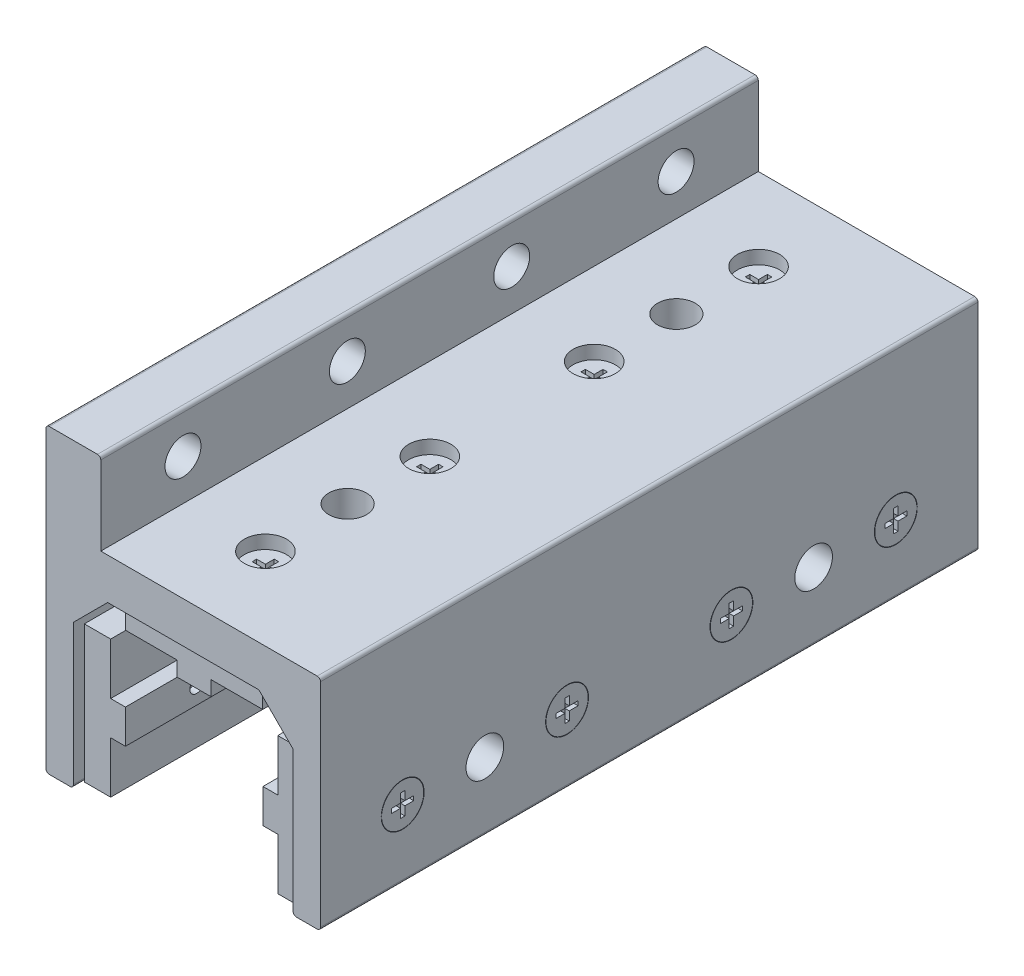
SolidWorks part; units mm, degrees
ref_plane "Front Plane" through (0, 0, 0) normal (0, 0, 1) x (1, 0, 0)
ref_plane "Top Plane" through (0, 0, 0) normal (0, 1, 0) x (1, 0, 0)
ref_plane "Right Plane" through (0, 0, 0) normal (1, 0, 0) x (0, 0, -1)
sketch "Sketch1" plane through (0, 0, 0) normal (0, 0, 1) x (1, 0, 0)
  line L0 (0, -34.925) -> (0, 34.925) construction
  line L1 (-31.8135, 0) -> (31.8135, 0) construction
  line L2 (-31.8135, 34.925) -> (-31.8135, -34.925) construction
  line L3 (-31.8135, -34.925) -> (-25.4635, -34.925) construction
  line L4 (-25.4635, -34.925) -> (-25.4635, -1.5875) construction
  line L5 (-25.4635, -1.5875) -> (-17.526, 6.35) construction
  line L6 (-17.526, 6.35) -> (17.526, 6.35) construction
  line L7 (17.526, 6.35) -> (25.4635, -1.5875) construction
  line L8 (25.4635, -1.5875) -> (25.4635, -34.925) construction
  line L9 (25.4635, -34.925) -> (31.8135, -34.925) construction
  line L10 (31.8135, -34.925) -> (31.8135, 15.875) construction
  line L11 (31.8135, 15.875) -> (-19.1135, 15.875) construction
  line L12 (-19.1135, 15.875) -> (-19.1135, 34.925) construction
  line L13 (-19.1135, 34.925) -> (-31.8135, 34.925) construction
  line L14 (-25.4635, -3.175) -> (-19.3675, -3.175) construction
  line L15 (-19.3675, -3.175) -> (-19.3675, -15.113) construction
  line L16 (-19.3675, -15.113) -> (-15.9385, -15.113) construction
  line L17 (-15.9385, -15.113) -> (-15.9385, -22.987) construction
  line L18 (-15.9385, -22.987) -> (-19.3675, -22.987) construction
  line L19 (-19.3675, -22.987) -> (-19.3675, -34.925) construction
  line L20 (-19.3675, -34.925) -> (-25.4635, -34.925) construction
  line L21 (-19.3675, -15.113) -> (-19.3675, -22.987) construction
  line L22 (-15.9385, -19.05) -> (-25.4635, -19.05) construction
  line L23 (-25.4635, -19.05) -> (25.4635, -19.05) construction
  point P4 (0, 0)
  point P7 (0, 0)
  point P30 (0, 6.35)
  point P31 (0, 12.7)
  dimension "Length (B)" = 69.85
  dimension "Length (A)" = 63.627
  dimension "Mounting Hole Depth" = 12.7
  dimension "D1" = 6.35
  dimension "Chamfer" = 7.9375
  dimension "D2" = 45
  dimension "Inner Height" = 41.275
  dimension "Pad Width" = 31.75
  dimension "Pad Height" = 9.525
  dimension "Pad Thickness" = 6.096
  dimension "Pad Rail" = 7.874
  dimension "Countersink Depth" = 3.175
  dimension "Length (C)" = 50.8
sketch "Sketch2" plane through (0, 0, 0) normal (1, 0, 0) x (0, 0, -1)
  line L0 (-76.2, 0) -> (76.2, 0) construction
  line L1 (-76.2, 15.875) -> (76.2, 15.875) construction
  line L2 (-76.2, 34.925) -> (76.2, 34.925) construction
  line L3 (-76.2, 34.925) -> (-76.2, -34.925) construction
  line L4 (-76.2, -34.925) -> (76.2, -34.925) construction
  line L5 (76.2, 34.925) -> (76.2, -34.925) construction
  line L6 (0, 34.925) -> (-76.2, 15.875) construction
  line L7 (0, 34.925) -> (0, 15.875) construction
  line L8 (-57.15, 25.4) -> (-19.05, 25.4) construction
  line L9 (-76.2, -19.05) -> (76.2, -19.05) construction
  line L10 (-57.6605, -21.6027) -> (-56.6395, -21.6027) construction
  line L11 (-57.6605, -21.6027) -> (-57.6605, -16.4973) construction
  line L12 (-57.6605, -16.4973) -> (-56.6395, -16.4973) construction
  line L13 (-56.6395, -21.6027) -> (-56.6395, -16.4973) construction
  line L14 (-57.15, -16.4973) -> (-57.15, -21.6027) construction
  line L15 (-57.6605, -19.05) -> (-56.6395, -19.05) construction
  line L16 (-59.7027, -18.5395) -> (-54.5973, -18.5395) construction
  line L17 (-59.7027, -18.5395) -> (-59.7027, -19.5605) construction
  line L18 (-59.7027, -19.5605) -> (-54.5973, -19.5605) construction
  line L19 (-54.5973, -18.5395) -> (-54.5973, -19.5605) construction
  line L20 (-57.15, -19.5605) -> (-57.15, -18.5395) construction
  line L21 (-59.7027, -19.05) -> (-54.5973, -19.05) construction
  line L22 (-38.1, 25.4) -> (-38.1, -19.05) construction
  circle A0 centre (-57.15, 25.4) radius 4.1656 construction
  circle A1 centre (-19.05, 25.4) radius 4.1656 construction
  circle A2 centre (-38.1, -19.05) radius 4.3688 construction
  circle A3 centre (-57.15, -19.05) radius 2.5527 construction
  circle A4 centre (-19.05, -19.05) radius 2.5527 construction
  circle A5 centre (-19.05, -19.05) radius 1.5875
  circle A6 centre (-57.15, -19.05) radius 1.5875
  point P12 (0, 15.875)
  point P39 (-38.1, 25.4)
  point P40 (0, -19.05)
  point P44 (-38.1, 25.4)
  dimension "Mounting Hole Diameter" = 8.3312
  dimension "Hole Diameter 2" = 8.7376
  dimension "D1" = 5.1054
  dimension "Pilot Hole" = 3.175
  dimension "Length" = 152.4
  dimension "Mounting Hole Spacing" = 38.1
  dimension "D2" = 1.0211
sketch "Sketch3" plane through (0, 0, 0) normal (0, 1, 0) x (1, 0, 0)
  line L0 (0, -76.2) -> (0, 76.2) construction
  line L5 (0, -76.2) -> (0, 76.2) construction
  circle A0 centre (0, -19.05) radius 2.5527 construction
  circle A1 centre (0, -57.15) radius 2.5527 construction
  circle A2 centre (0, -38.1) radius 4.3688 construction
  circle A3 centre (0, -19.05) radius 4.8895 construction
  circle A4 centre (0, -57.15) radius 4.8895 construction
  dimension "D1" = 8.7376
  dimension "D2" = 5.1054
  dimension "Countersink Diameter" = 9.779
ref_plane "Plane1" through (0, 0, 57.15) normal (0, 0, 1) x (1, 0, 0)
sketch "Sketch11" plane through (0, 0, 57.15) normal (0, 0, 1) x (1, 0, 0)
  line L0 (-25.4635, -19.05) -> (-31.8135, -19.05) construction
  line L1 (-31.8135, 34.925) -> (-31.8135, -34.925) construction
  line L2 (-31.8135, -14.1605) -> (-31.8135, -23.9395) construction
  line L3 (-31.8135, -14.1605) -> (-29.7355, -16.637) construction
  line L4 (-29.7355, -16.637) -> (-29.7355, -21.463) construction
  line L5 (-29.7355, -21.463) -> (-31.8135, -23.9395) construction
  line L6 (-29.7355, -16.637) -> (-17.653, -16.637) construction
  line L7 (-17.653, -16.637) -> (-17.653, -15.113) construction
  line L8 (-19.3675, -15.113) -> (-15.9385, -15.113) construction
  point P7 (-30.7745, -15.3987)
  dimension "D1" = 9.779
  dimension "D2" = 100
  dimension "D3" = 4.826
sketch "Sketch4" plane through (0, 0, 0) normal (0, 0, 1) x (1, 0, 0)
  line L0 (-31.8135, -34.925) -> (-25.4635, -34.925) construction
  line L1 (-31.8135, 34.925) -> (-31.8135, -34.925) construction
  line L2 (-19.1135, 34.925) -> (-31.8135, 34.925) construction
  line L3 (-19.1135, 15.875) -> (-19.1135, 34.925) construction
  line L4 (31.8135, 15.875) -> (-19.1135, 15.875) construction
  line L5 (31.8135, -34.925) -> (31.8135, 15.875) construction
  line L6 (25.4635, -34.925) -> (31.8135, -34.925) construction
  line L7 (25.4635, -1.5875) -> (25.4635, -34.925) construction
  line L8 (17.526, 6.35) -> (25.4635, -1.5875) construction
  line L9 (-17.526, 6.35) -> (17.526, 6.35) construction
  line L10 (-25.4635, -1.5875) -> (-17.526, 6.35) construction
  line L11 (-25.4635, -34.925) -> (-25.4635, -1.5875) construction
  line L12 (-31.8135, -34.925) -> (-25.4635, -34.925)
  line L13 (-31.8135, 34.925) -> (-31.8135, -34.925)
  line L14 (-19.1135, 34.925) -> (-31.8135, 34.925)
  line L15 (-19.1135, 15.875) -> (-19.1135, 34.925)
  line L16 (31.8135, 15.875) -> (-19.1135, 15.875)
  line L17 (31.8135, -34.925) -> (31.8135, 15.875)
  line L18 (25.4635, -34.925) -> (31.8135, -34.925)
  line L19 (25.4635, -1.5875) -> (25.4635, -34.925)
  line L20 (17.526, 6.35) -> (25.4635, -1.5875)
  line L21 (-17.526, 6.35) -> (17.526, 6.35)
  line L22 (-25.4635, -1.5875) -> (-17.526, 6.35)
  line L23 (-25.4635, -34.925) -> (-25.4635, -1.5875)
extrude "Boss-Extrude1" add sketch "Sketch4" along normal up to vertex (76.2 mm away) up to point (0, 34.925, 76.2)
sketch "Sketch5" plane through (0, 0, 0) normal (0, 0, 1) x (1, 0, 0)
  line L0 (-25.4635, -3.175) -> (-25.4635, -34.925)
  line L1 (-25.4635, -34.925) -> (-19.3675, -34.925)
  line L2 (-19.3675, -34.925) -> (-19.3675, -22.987)
  line L3 (-19.3675, -22.987) -> (-15.9385, -22.987)
  line L4 (-15.9385, -22.987) -> (-15.9385, -15.113)
  line L5 (-15.9385, -15.113) -> (-19.3675, -15.113)
  line L6 (-19.3675, -15.113) -> (-19.3675, -3.175)
  line L7 (-19.3675, -3.175) -> (-25.4635, -3.175)
extrude "Boss-Extrude2" add sketch "Sketch5" along normal offset from surface (71.12 mm away) 2.54 from offset 2.54 separate body up to face at (-3.1856, -2.3812, 76.2)
sketch "Sketch6" plane through (0, 0, 0) normal (1, 0, 0) x (0, 0, -1)
  circle A0 centre (-57.15, -19.05) radius 2.5527 construction
  circle A1 centre (-38.1, -19.05) radius 4.3688 construction
  circle A2 centre (-19.05, -19.05) radius 2.5527 construction
  circle A3 centre (-19.05, 25.4) radius 4.1656 construction
  circle A4 centre (-57.15, 25.4) radius 4.1656 construction
  circle A5 centre (-57.15, -19.05) radius 2.5527
  circle A6 centre (-38.1, -19.05) radius 4.3688
  circle A7 centre (-19.05, -19.05) radius 2.5527
  circle A8 centre (-19.05, 25.4) radius 4.1656
  circle A9 centre (-57.15, 25.4) radius 4.1656
extrude "Cut-Extrude1" cut sketch "Sketch6" against normal through all both and the other way through all
sketch "Sketch7" plane through (0, 0, 0) normal (1, 0, 0) x (0, 0, -1)
  line L1 (-42.4688, -23.4188) -> (-33.7312, -23.4188)
  line L2 (-42.4688, -23.4188) -> (-42.4688, -14.6812)
  line L3 (-42.4688, -14.6812) -> (-33.7312, -14.6812)
  line L4 (-33.7312, -23.4188) -> (-33.7312, -14.6812)
  line L5 (-38.1, -14.6812) -> (-38.1, -23.4188) construction
  line L6 (-42.4688, -19.05) -> (-33.7312, -19.05) construction
  circle A0 centre (-57.15, -19.05) radius 1.5875 construction
  circle A1 centre (-57.15, -19.05) radius 1.5875
  circle A2 centre (-19.05, -19.05) radius 1.5875 construction
  circle A3 centre (-19.05, -19.05) radius 1.5875
  circle A4 centre (-38.1, -19.05) radius 4.3688 construction
  point P6 (-38.1, -19.05)
extrude "Cut-Extrude2" cut sketch "Sketch7" against normal through all
sketch "Sketch8" plane through (0, 15.875, 0) normal (0, 1, 0) x (1, 0, 0)
  circle A0 centre (0, -19.05) radius 2.5527 construction
  circle A1 centre (0, -57.15) radius 2.5527 construction
  circle A2 centre (0, -19.05) radius 2.5527
  circle A3 centre (0, -57.15) radius 2.5527
extrude "Cut-Extrude3" cut sketch "Sketch8" against normal up to vertex (9.525 mm away) up to point (0, 6.35, 0)
sketch "Sketch9" plane through (0, 15.875, 0) normal (0, 1, 0) x (1, 0, 0)
  circle A0 centre (0, -19.05) radius 4.8895 construction
  circle A1 centre (0, -19.05) radius 4.8895
  circle A2 centre (0, -57.15) radius 4.8895 construction
  circle A3 centre (0, -57.15) radius 4.8895
extrude "Cut-Extrude4" cut sketch "Sketch9" against normal up to vertex (3.175 mm away) up to point (0, 12.7, 0)
chamfer "Chamfer1" distance 2.032 angle 50 6 edges at (-31.8135, -19.05, 16.4973) (-31.8135, -19.05, 54.5973) (31.8135, -19.05, 16.4973) (31.8135, -19.05, 54.5973) (-2.5527, 12.7, 57.15) (-2.5527, 12.7, 19.05)
sketch "Sketch12" plane through (0, 0, 57.15) normal (0, 0, 1) x (1, 0, 0)
  line L0 (-31.8135, -14.1605) -> (-31.8135, -19.05)
  line L1 (-31.8135, -19.05) -> (-17.653, -19.05)
  line L2 (-17.653, -19.05) -> (-17.653, -16.637)
  line L3 (-17.653, -16.637) -> (-29.7355, -16.637)
  line L4 (-29.7355, -16.637) -> (-31.8135, -14.1605)
revolve "Revolve1" add sketch "Sketch12" angle 360 about L1
sketch "Sketch13" plane through (-31.8135, 0, 0) normal (-1, 0, 0) x (0, 0, 1)
  line L0 (57.6605, -21.6027) -> (56.6395, -21.6027) construction
  line L1 (57.6605, -21.6027) -> (57.6605, -16.4973) construction
  line L2 (57.6605, -16.4973) -> (56.6395, -16.4973) construction
  line L3 (56.6395, -21.6027) -> (56.6395, -16.4973) construction
  line L4 (57.6605, -21.6027) -> (56.6395, -21.6027)
  line L5 (57.6605, -21.6027) -> (57.6605, -19.5605)
  line L6 (57.6605, -16.4973) -> (56.6395, -16.4973)
  line L7 (56.6395, -21.6027) -> (56.6395, -19.5605)
  line L8 (59.7027, -18.5395) -> (59.7027, -19.5605) construction
  line L9 (59.7027, -19.5605) -> (54.5973, -19.5605) construction
  line L10 (54.5973, -18.5395) -> (54.5973, -19.5605) construction
  line L11 (59.7027, -18.5395) -> (54.5973, -18.5395) construction
  line L12 (59.7027, -18.5395) -> (59.7027, -19.5605)
  line L13 (59.7027, -19.5605) -> (57.6605, -19.5605)
  line L14 (54.5973, -18.5395) -> (54.5973, -19.5605)
  line L15 (59.7027, -18.5395) -> (57.6605, -18.5395)
  line L16 (56.6395, -18.5395) -> (54.5973, -18.5395)
  line L17 (56.6395, -18.5395) -> (56.6395, -16.4973)
  line L18 (56.6395, -19.5605) -> (54.5973, -19.5605)
  line L19 (57.6605, -18.5395) -> (57.6605, -16.4973)
extrude "Cut-Extrude5" cut sketch "Sketch13" against normal up to vertex (1.039 mm away) up to point (-30.7745, -15.3987, 57.15)
pattern_linear "LPattern1" count 2 spacing 38.1 along (0, 0, -1) of bodies 111
pattern_circular "CirPattern1" count 3 over 180 about axis through (0, -19.05, 0) along (0, 0, 1) of bodies 107 111 112
fillet "Fillet1" radius 0.762 7 edges at (-19.1135, 34.925, 38.1) (-31.8135, 34.925, 38.1) (31.8135, 15.875, 38.1) (31.8135, -34.925, 38.1) (25.4635, -34.925, 38.1) (-25.4635, -34.925, 38.1) (-31.8135, -34.925, 38.1)
sketch "Sketch14" plane through (0, 15.875, 0) normal (0, 1, 0) x (1, 0, 0)
  circle A0 centre (0, -38.1) radius 4.3688
  circle A1 centre (0, -38.1) radius 4.3688 construction
extrude "Cut-Extrude6" cut sketch "Sketch14" against normal through all
mirror "Mirror1" about plane through (0, 0, 0) normal (0, 0, 1) of bodies 119 107 113 114 116 118 117 115 112 111
combine bodies "Combine1" operation type add bodies to combine 119 122
equation "\"D1@Sketch1\" = \"Mounting Hole Depth@Sketch1\" / 2"
equation "\"D1@Sketch3\"=\"Hole Diameter 2@Sketch2\""
equation "\"D2@Sketch3\"=\"D1@Sketch2\""
equation "\"D2@Sketch2\"=\"D1@Sketch2\"*.2"
equation "\"D1@Sketch11\"=\"Countersink Diameter@Sketch3\""
equation "\"D3@LPattern1\"=\"Mounting Hole Spacing@Sketch2\""
equation "\"Chamfer@Sketch1\"=\"Mounting Hole Depth@Sketch1\"*.625"
